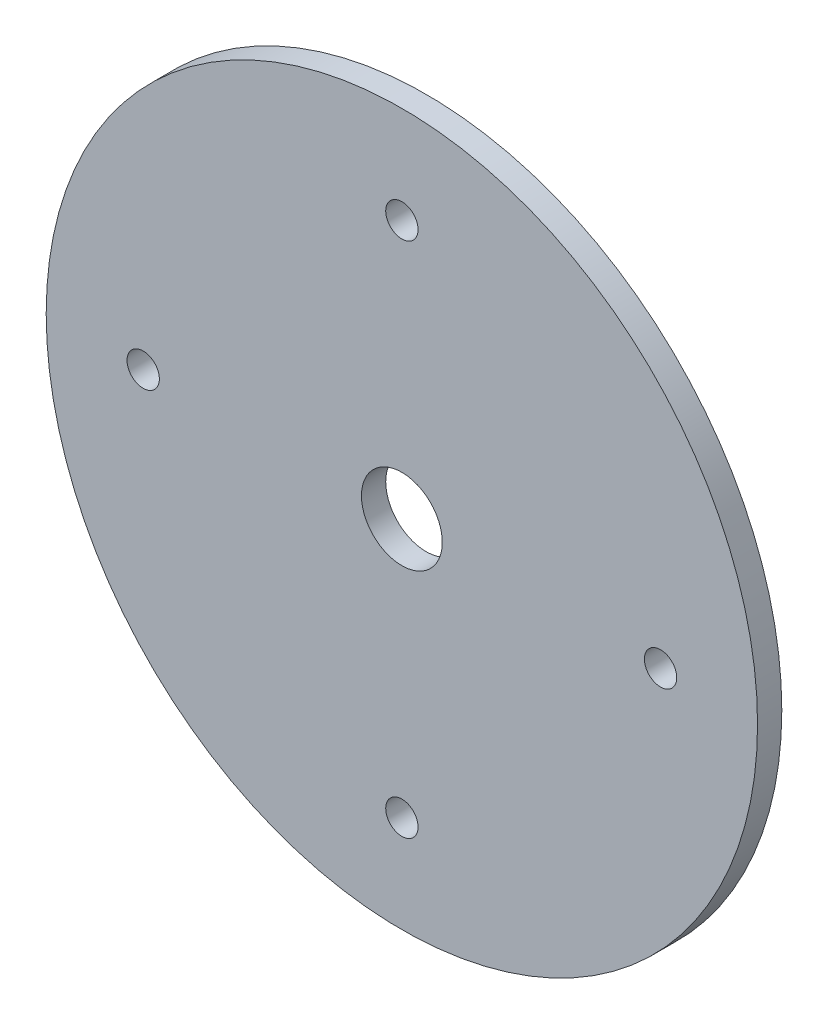
SolidWorks part; units mm, degrees
ref_plane "前视基准面" through (0, 0, 0) normal (0, 0, 1) x (1, 0, 0)
ref_plane "上视基准面" through (0, 0, 0) normal (0, 1, 0) x (1, 0, 0)
ref_plane "右视基准面" through (0, 0, 0) normal (1, 0, 0) x (0, 0, -1)
sketch "草图2" plane through (0, 0, 0) normal (0, 0, 1) x (1, 0, 0)
  line L1 (-6, -20.3) -> (6, -20.3)
  line L2 (6, -20.3) -> (7.4798, -16.1522)
  line L3 (-6, -20.3) -> (-7.4798, -16.1522)
  arc A0 (7.4798, -16.1522) -> (-7.4798, -16.1522) centre (0, 0) ccw
extrude "凸台-拉伸1" add sketch "草图2" along normal blind 1.5
sketch "草图3" plane through (0, 0, 1.5) normal (0, 0, 1) x (1, 0, 0)
  circle A0 centre (0, 0) radius 22
extrude "凸台-拉伸2" add sketch "草图3" along normal blind 1.5
sketch "草图4" plane through (0, 0, 0) normal (0, 0, -1) x (-1, 0, 0)
  circle A0 centre (0, 0) radius 35.0705
extrude "切除-拉伸1" cut sketch "草图4" against normal blind 1.5
sketch "草图5" plane through (0, 0, 1.5) normal (0, 0, -1) x (-1, 0, 0)
  circle A1 centre (0, 16) radius 1
  circle A2 centre (-16, 0) radius 1
  circle A3 centre (0, -16) radius 1
  circle A4 centre (16, 0) radius 1
extrude "切除-拉伸2" cut sketch "草图5" against normal blind 1.5
sketch "草图6" plane through (0, 0, 1.5) normal (0, 0, -1) x (-1, 0, 0)
  circle A0 centre (0, 0) radius 2.5
extrude "切除-拉伸3" cut sketch "草图6" against normal blind 1.5
